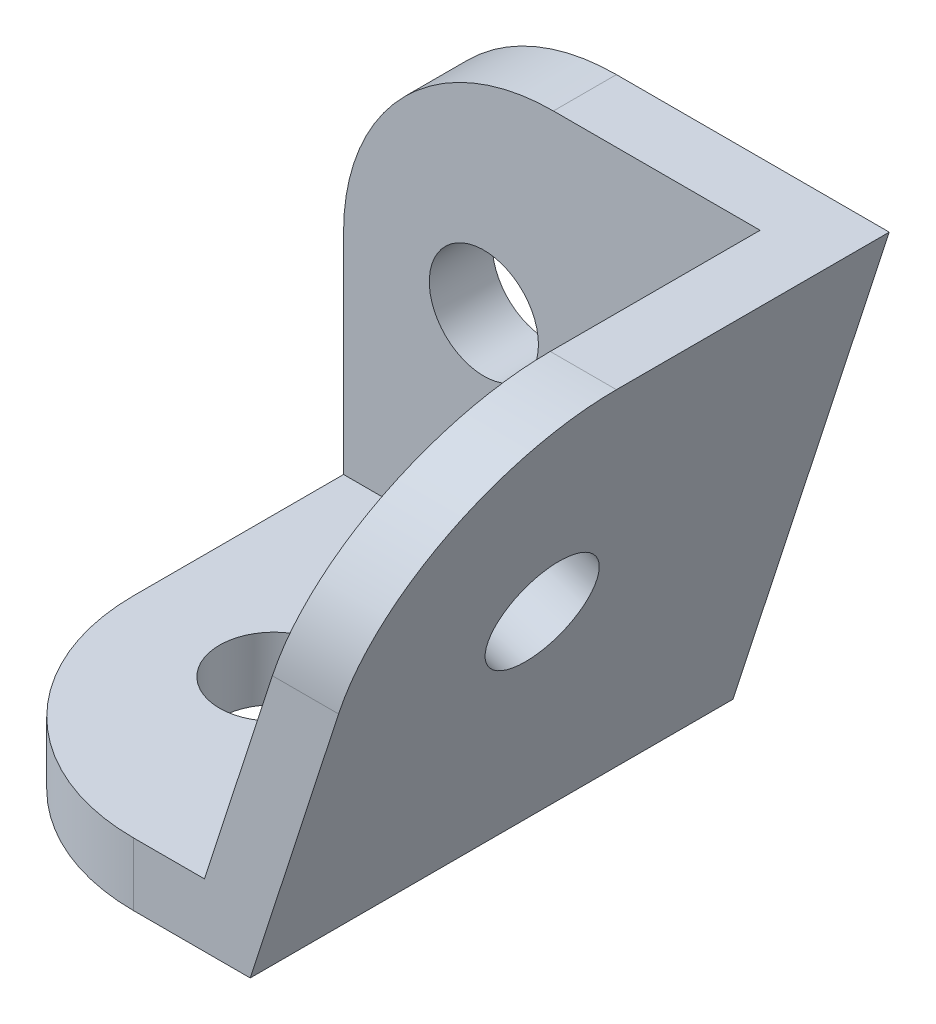
SolidWorks part; units mm, degrees
ref_plane "Plan de face" through (0, 0, 0) normal (0, 0, 1) x (1, 0, 0)
ref_plane "Plan de dessus" through (0, 0, 0) normal (0, 1, 0) x (1, 0, 0)
ref_plane "Plan de droite" through (0, 0, 0) normal (1, 0, 0) x (0, 0, -1)
sketch "Esquisse1" plane through (0, 0, 0) normal (0, 0, 1) x (1, 0, 0)
  line L0 (55.4188, 3) -> (55.4188, 26)
  line L1 (70, 3) -> (0, 3) construction
  line L2 (55.4188, 26) -> (78.4188, 26)
  line L3 (100, 92.65) -> (70, 0) construction
  line L4 (78.4188, 26) -> (70.9714, 3)
  line L5 (70.9714, 3) -> (55.4188, 3)
  dimension "D1" = 23
  dimension "D2" = 23
extrude "Boss.-Extru.1" add sketch "Esquisse1" along normal blind 3
sketch "Esquisse2" plane through (63.3572, -20.515, 0) normal (-0.9514, 0.3081, 0) x (0, 0, 1)
  line L2 (3, 48.8927) -> (23, 48.8927)
  line L3 (3, 48.8927) -> (3, 24.717)
  line L4 (3, 24.717) -> (23, 24.717)
  line L5 (23, 48.8927) -> (23, 24.717)
  point P0 (0, 0)
  dimension "D1" = 20
extrude "Boss.-Extru.2" add sketch "Esquisse2" along normal blind 3
sketch "Esquisse3" plane through (0, 0, 3) normal (0, 0, 1) x (1, 0, 0)
  line L1 (55.4188, 3) -> (70.9714, 3)
  line L2 (55.4188, 3) -> (55.4188, 6)
  line L3 (55.4188, 6) -> (70.9714, 6)
  line L4 (70.9714, 3) -> (70.9714, 6)
  point P5 (0, 0)
  dimension "D1" = 3
extrude "Boss.-Extru.3" add sketch "Esquisse3" along normal up to surface (20 mm away) up to face at (73.268, 14.9621, 23)
sketch "Esquisse4" plane through (0, 0, 23) normal (0, 0, 1) x (1, 0, 0)
  line L0 (78.4188, 26) -> (75.2654, 26)
  line L1 (68.7894, 6) -> (75.5647, 26.9242) construction
  line L2 (70.9714, 3) -> (55.4188, 3) construction
  line L3 (75.2654, 26) -> (75.5647, 26.9242)
  line L4 (75.5647, 26.9242) -> (78.4188, 26)
extrude "Enlèv. mat.-Extru.1" cut sketch "Esquisse4" against normal blind 20
fillet "Congé1" radius 10 3 edges at (76.8421, 26, 23) (55.4188, 4.5, 23) (55.4188, 26, 1.5)
sketch "Esquisse5" plane through (0, 0, 3) normal (0, 0, 1) x (1, 0, 0)
  line L0 (62.1041, 6) -> (62.1041, 23.8834) construction
  line L1 (68.7894, 6) -> (55.4188, 6) construction
  circle A0 centre (62.1041, 16) radius 2.6
  dimension "D1" = 5.2
  dimension "D2" = 10
extrude "Enlèv. mat.-Extru.2" cut sketch "Esquisse5" against normal blind 20
sketch "Esquisse6" plane through (0, 6, 0) normal (0, 1, 0) x (1, 0, 0)
  line L0 (62.1041, -3) -> (62.1041, -22.1901) construction
  line L1 (68.7894, -3) -> (55.4188, -3) construction
  circle A0 centre (62.1041, -13) radius 2.6
  point P6 (0, 0)
  point P7 (62.1041, -3)
  dimension "D1" = 5.2
  dimension "D2" = 10
extrude "Enlèv. mat.-Extru.3" cut sketch "Esquisse6" against normal blind 20
sketch "Esquisse7" plane through (60.5031, -19.5909, 0) normal (-0.9514, 0.3081, 0) x (0, 0, 1)
  line L0 (3, 37.4102) -> (20.7953, 37.4102) construction
  line L1 (3, 47.9213) -> (3, 26.899) construction
  line L2 (13, 26.899) -> (13, 46.1797) construction
  line L3 (3, 26.899) -> (23, 26.899) construction
  circle A0 centre (13, 37.4102) radius 2.6
  dimension "D1" = 5.2
extrude "Enlèv. mat.-Extru.4" cut sketch "Esquisse7" against normal blind 20
